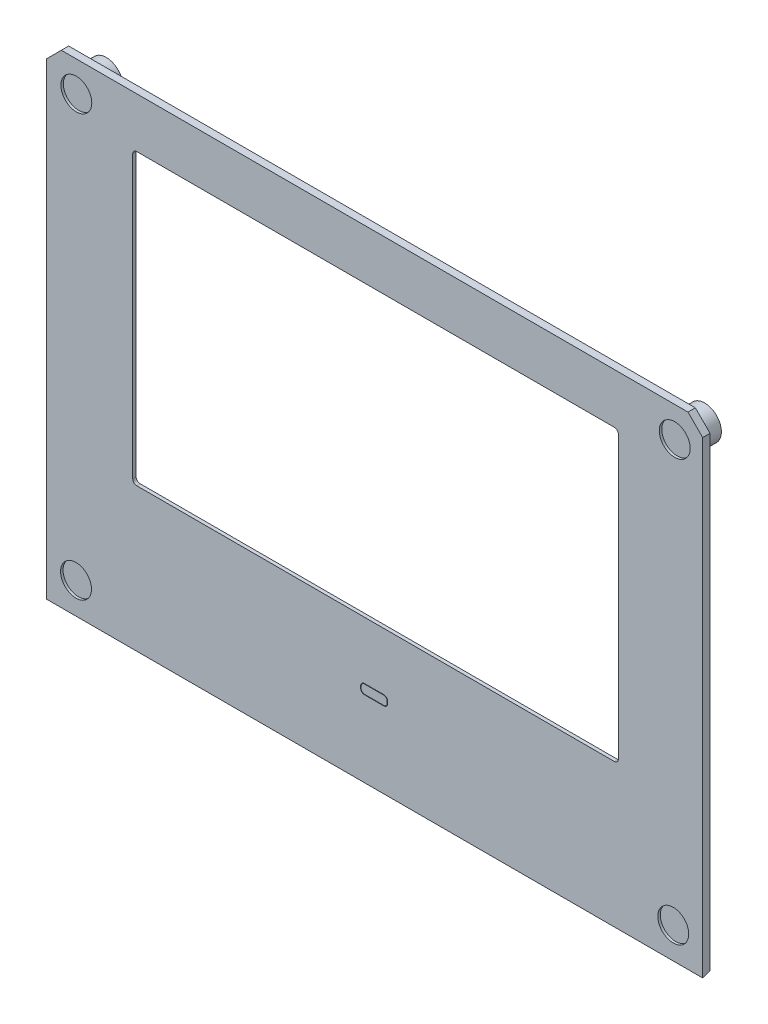
SolidWorks part; units mm, degrees
ref_plane "Front Plane" through (0, 0, 0) normal (0, 0, 1) x (1, 0, 0)
ref_plane "Top Plane" through (0, 0, 0) normal (0, 1, 0) x (1, 0, 0)
ref_plane "Right Plane" through (0, 0, 0) normal (1, 0, 0) x (0, 0, -1)
sketch "Sketch1" plane through (0, 0, 0) normal (0, 0, 1) x (1, 0, 0)
  line L0 (0, 0) -> (0, 2.5) construction
  line L2 (-49.5, -27) -> (49.5, -27)
  line L3 (-49.5, -27) -> (-49.5, 32)
  line L4 (-49.5, 32) -> (49.5, 32)
  line L5 (49.5, -27) -> (49.5, 32)
  line L6 (-49.5, -27) -> (49.5, 32) construction
  line L7 (-49.5, 32) -> (49.5, -27) construction
  line L16 (63.7, 42.2) -> (-64.0602, 42.2)
  line L17 (-64.0602, 42.2) -> (-67.0602, 39.2)
  line L18 (-67.0602, 39.2) -> (-67.0602, -42.1345)
  line L19 (-67.0602, -42.1345) -> (-67.0602, -55.3)
  line L20 (-67.0602, -55.3) -> (66.7, -55.3)
  line L21 (66.7, -55.3) -> (66.7, -42.1345)
  line L22 (66.7, -42.1345) -> (66.7, 39.2)
  line L23 (66.7, 39.2) -> (63.7, 42.2)
  dimension "D3" = 99
  dimension "D6" = 59
  dimension "D7" = 2.5
  dimension "D1" = 97.5
extrude "Boss-Extrude1" add sketch "Sketch1" along normal blind 1.5
sketch "Sketch2" plane through (-67.0602, 0, 0) normal (-1, 0, 0) x (0, 0, 1)
  line L1 (0, 39.2) -> (0, -55.3) construction
  line L2 (1.5684, -56.2492) -> (-60.7101, -33.5817)
  line L3 (1.5684, -56.2492) -> (-60.7101, -33.5817)
  line L4 (0, 39.2) -> (0, -55.3)
  line L5 (1.5, 39.2) -> (1.5, -55.3) construction
  line L6 (1.5, 39.2) -> (1.5, -55.3)
  line L7 (1.5, -55.3) -> (0, -55.3) construction
  line L8 (1.5, -55.3) -> (0, -55.3)
  line L9 (1.5, -55.3) -> (1.5, -56.4371)
  line L10 (0, -55.3) -> (0, -55.8912)
  line M3 (0, -55.3) -> (1.5, -55.3)
  dimension "D1" = 0.2
extrude "Boss-Extrude2" add sketch "Sketch2" against normal up to surface (133.7602 mm away) contours L10 L3 L9 M3 region at (-67.0602, -55.6447, 0.8548) up to face at (66.7, -8.05, 0.75)
sketch "Sketch3" plane through (0, 0, 0) normal (0, 0, -1) x (-1, 0, 0)
  line L0 (54.4999, -35.4999) -> (54.4999, 35.5001)
  line L1 (54.4999, 35.5001) -> (-54.5001, 35.5001)
  line L2 (-54.5001, 35.5001) -> (-54.5001, -35.4999)
  line L3 (-54.5001, -35.4999) -> (54.4999, -35.4999)
  line L4 (52.9999, -33.9999) -> (52.9999, 34.0001)
  line L5 (-53.0001, -33.9999) -> (52.9999, -33.9999)
  line L6 (-53.0001, 34.0001) -> (-53.0001, -33.9999)
  line L7 (52.9999, 34.0001) -> (-53.0001, 34.0001)
  line L8 (52.9999, -33.9999) -> (52.9999, 34.0001) construction
  line L9 (-53.0001, -33.9999) -> (52.9999, -33.9999) construction
  line L10 (-53.0001, 34.0001) -> (-53.0001, -33.9999) construction
  line L11 (52.9999, 34.0001) -> (-53.0001, 34.0001) construction
  dimension "D1" = 0
  dimension "D2" = 1.5
extrude "Cut-Extrude1" cut sketch "Sketch3" against normal blind 0.8
sketch "Sketch4" plane through (0, 0, 1.5) normal (0, 0, 1) x (1, 0, 0)
  circle A0 centre (60.7, -49.8912) radius 1.5 construction
  circle A1 centre (-61.0602, -49.8912) radius 1.5 construction
  circle A2 centre (60.7, -49.8912) radius 1.5
  circle A3 centre (-61.0602, -49.8912) radius 1.5
  spline S0 degree 3 poles (-62.625, 36) (-62.625, 32.75) (-59.375, 32.75) (-59.375, 36) (-59.375, 39.25) (-62.625, 39.25) (-62.625, 36) (-62.625, 32.75) (-59.375, 32.75) knots -0.5 0 0 0 0.5 0.5 0.5 1 1 1 1.5 1.5 1.5 weights 1 0.333333 0.333333 1 0.333333 0.333333 1 0.333333 0.333333 only from (-62.625, 36) to (-62.625, 36) construction
  spline S1 degree 3 poles (-62.625, 36) (-62.625, 32.75) (-59.375, 32.75) (-59.375, 36) (-59.375, 39.25) (-62.625, 39.25) (-62.625, 36) (-62.625, 32.75) (-59.375, 32.75) knots -0.5 0 0 0 0.5 0.5 0.5 1 1 1 1.5 1.5 1.5 weights 1 0.333333 0.333333 1 0.333333 0.333333 1 0.333333 0.333333 only from (-62.625, 36) to (-62.625, 36)
  spline S2 degree 3 poles (59.375, 36) (59.375, 32.75) (62.625, 32.75) (62.625, 36) (62.625, 39.25) (59.375, 39.25) (59.375, 36) (59.375, 32.75) (62.625, 32.75) knots -0.5 0 0 0 0.5 0.5 0.5 1 1 1 1.5 1.5 1.5 weights 1 0.333333 0.333333 1 0.333333 0.333333 1 0.333333 0.333333 only from (59.375, 36) to (59.375, 36) construction
  spline S3 degree 3 poles (59.375, 36) (59.375, 32.75) (62.625, 32.75) (62.625, 36) (62.625, 39.25) (59.375, 39.25) (59.375, 36) (59.375, 32.75) (62.625, 32.75) knots -0.5 0 0 0 0.5 0.5 0.5 1 1 1 1.5 1.5 1.5 weights 1 0.333333 0.333333 1 0.333333 0.333333 1 0.333333 0.333333 only from (59.375, 36) to (59.375, 36)
  spline S4 degree 3 poles (-62.625, -36) (-62.625, -39.25) (-59.375, -39.25) (-59.375, -36) (-59.375, -32.75) (-62.625, -32.75) (-62.625, -36) (-62.625, -39.25) (-59.375, -39.25) knots -0.5 0 0 0 0.5 0.5 0.5 1 1 1 1.5 1.5 1.5 weights 1 0.333333 0.333333 1 0.333333 0.333333 1 0.333333 0.333333 only from (-62.625, -36) to (-62.625, -36) construction
  spline S5 degree 3 poles (-62.625, -36) (-62.625, -39.25) (-59.375, -39.25) (-59.375, -36) (-59.375, -32.75) (-62.625, -32.75) (-62.625, -36) (-62.625, -39.25) (-59.375, -39.25) knots -0.5 0 0 0 0.5 0.5 0.5 1 1 1 1.5 1.5 1.5 weights 1 0.333333 0.333333 1 0.333333 0.333333 1 0.333333 0.333333 only from (-62.625, -36) to (-62.625, -36) construction
  spline S6 degree 3 poles (59.375, -36) (59.375, -39.25) (62.625, -39.25) (62.625, -36) (62.625, -32.75) (59.375, -32.75) (59.375, -36) (59.375, -39.25) (62.625, -39.25) knots -0.5 0 0 0 0.5 0.5 0.5 1 1 1 1.5 1.5 1.5 weights 1 0.333333 0.333333 1 0.333333 0.333333 1 0.333333 0.333333 only from (59.375, -36) to (59.375, -36) construction
  spline S7 degree 3 poles (59.375, -36) (59.375, -39.25) (62.625, -39.25) (62.625, -36) (62.625, -32.75) (59.375, -32.75) (59.375, -36) (59.375, -39.25) (62.625, -39.25) knots -0.5 0 0 0 0.5 0.5 0.5 1 1 1 1.5 1.5 1.5 weights 1 0.333333 0.333333 1 0.333333 0.333333 1 0.333333 0.333333 only from (59.375, -36) to (59.375, -36) construction
extrude "Cut-Extrude2" cut sketch "Sketch4" against normal blind 2
sketch "Sketch5" plane through (0, 0, 1.5) normal (0, 0, 1) x (1, 0, 0)
  line L4 (-57, 36) -> (-57, 40.2)
  line L5 (-57, 40.2) -> (-61, 40.2)
  line L6 (-65.2, 36) -> (-65.2, 32)
  line L7 (-65.2, 32) -> (-61, 32)
  line L8 (-57, 36) -> (-57, 40.2) construction
  line L9 (-57, 40.2) -> (-61, 40.2) construction
  line L10 (-65.2, 36) -> (-65.2, 32) construction
  line L11 (-65.2, 32) -> (-61, 32) construction
  line L12 (61, 40.2) -> (57, 40.2)
  line L13 (57, 40.2) -> (57, 36)
  line L14 (61, 32) -> (65.2, 32)
  line L15 (65.2, 32) -> (65.2, 36)
  line L16 (61, 40.2) -> (57, 40.2) construction
  line L17 (57, 40.2) -> (57, 36) construction
  line L18 (61, 32) -> (65.2, 32) construction
  line L19 (65.2, 32) -> (65.2, 36) construction
  circle A0 centre (-61, 36) radius 1.625 construction
  circle A1 centre (-61, 36) radius 1.625
  circle A2 centre (61, 36) radius 1.625 construction
  circle A3 centre (61, 36) radius 1.625
  arc A8 (-61, 40.2) -> (-65.2, 36) centre (-61.0002, 36.0002) ccw
  arc A9 (-61, 32) -> (-57, 36) centre (-61, 36) ccw
  arc A10 (-61, 40.2) -> (-65.2, 36) centre (-61.0002, 36.0002) ccw construction
  arc A11 (-61, 32) -> (-57, 36) centre (-61, 36) ccw construction
  arc A12 (65.2, 36) -> (61, 40.2) centre (61.0002, 36.0002) ccw
  arc A13 (57, 36) -> (61, 32) centre (61, 36) ccw
  arc A14 (65.2, 36) -> (61, 40.2) centre (61.0002, 36.0002) ccw construction
  arc A15 (57, 36) -> (61, 32) centre (61, 36) ccw construction
  circle A16 centre (-61, 36) radius 3.3998
  circle A17 centre (61.0002, 36.0002) radius 3.3998
  dimension "D3" = 0.8
  dimension "D1" = 0
  dimension "D2" = 0
extrude "Boss-Extrude3" add sketch "Sketch5" against normal offset from surface (6.1114 mm away) 1.7
sketch "Sketch6" plane through (0, 0, 1.5) normal (0, 0, 1) x (1, 0, 0)
  line L4 (3.5199, -36.2) -> (-11.8801, -36.2)
  line L5 (-11.8801, -36.2) -> (-11.8801, -48.2)
  line L6 (-11.8801, -48.2) -> (3.5199, -48.2)
  line L7 (3.5199, -48.2) -> (3.5199, -36.2)
  line L8 (3.5199, -36.2) -> (-11.8801, -36.2) construction
  line L9 (-11.8801, -36.2) -> (-11.8801, -48.2) construction
  line L10 (-11.8801, -48.2) -> (3.5199, -48.2) construction
  line L11 (3.5199, -48.2) -> (3.5199, -36.2) construction
  circle A0 centre (-0.2801, -39.7) radius 3.5
  circle A1 centre (-0.2801, -39.7) radius 2.5
  circle A2 centre (-0.2801, -39.7) radius 2.5 construction
  dimension "D3" = 7
  dimension "D1" = 0
  dimension "D2" = 0
extrude "Cut-Extrude5" cut sketch "Sketch6" against normal blind 10
sketch "Sketch7" plane through (0, 0, 1.5) normal (0, 0, 1) x (1, 0, 0)
  line L1 (-3.0301, -40.7) -> (2.4699, -40.7)
  line L2 (-3.0301, -40.7) -> (-3.0301, -38.7)
  line L3 (-3.0301, -38.7) -> (2.4699, -38.7)
  line L4 (2.4699, -40.7) -> (2.4699, -38.7)
  line L5 (-3.0301, -40.7) -> (2.4699, -38.7) construction
  line L6 (-3.0301, -38.7) -> (2.4699, -40.7) construction
  circle A0 centre (-0.2801, -39.7) radius 3.5 construction
  circle A1 centre (-0.2801, -39.7) radius 3.5
  dimension "D1" = 5.5
  dimension "D2" = 2
extrude "Boss-Extrude4" add sketch "Sketch7" against normal blind 0.8
fillet "Fillet1" radius 0.8 4 edges at (2.4699, -40.7, 1.1) (2.4699, -38.7, 1.1) (-3.0301, -40.7, 1.1) (-3.0301, -38.7, 1.1)
sketch "Sketch8" plane through (0, 0, 0.7) normal (0, 0, -1) x (-1, 0, 0)
  circle A0 centre (0.2801, -39.7) radius 3.25
  circle A1 centre (0.2801, -39.7) radius 3.5 construction
  dimension "D1" = 0.25
  dimension "D2" = 6.5
extrude "Boss-Extrude5" add sketch "Sketch8" along normal blind 1.5 separate body
sketch "Sketch9" plane through (0, 0, 0.7) normal (0, 0, 1) x (1, 0, 0)
  line L9 (2.3699, -39.9) -> (2.3699, -39.5)
  line L10 (-2.2301, -40.6) -> (1.6699, -40.6)
  line L11 (-2.9301, -39.5) -> (-2.9301, -39.9)
  line L12 (1.6699, -38.8) -> (-2.2301, -38.8)
  line L13 (2.3699, -39.9) -> (2.3699, -39.5)
  line L14 (-2.2301, -40.6) -> (1.6699, -40.6)
  line L15 (-2.9301, -39.5) -> (-2.9301, -39.9)
  line L16 (1.6699, -38.8) -> (-2.2301, -38.8)
  arc A8 (1.6699, -40.6) -> (2.3699, -39.9) centre (1.6699, -39.9) ccw
  arc A9 (-2.9301, -39.9) -> (-2.2301, -40.6) centre (-2.2301, -39.9) ccw
  arc A10 (-2.2301, -38.8) -> (-2.9301, -39.5) centre (-2.2301, -39.5) ccw
  arc A11 (2.3699, -39.5) -> (1.6699, -38.8) centre (1.6699, -39.5) ccw
  arc A12 (1.6699, -40.6) -> (2.3699, -39.9) centre (1.6699, -39.9) ccw
  arc A13 (-2.9301, -39.9) -> (-2.2301, -40.6) centre (-2.2301, -39.9) ccw
  arc A14 (-2.2301, -38.8) -> (-2.9301, -39.5) centre (-2.2301, -39.5) ccw
  arc A15 (2.3699, -39.5) -> (1.6699, -38.8) centre (1.6699, -39.5) ccw
  dimension "D1" = 0.1
extrude "Boss-Extrude6" add sketch "Sketch9" along normal up to surface (0.8 mm away) up to face at (-59.5602, -49.8912, 1.5)
fillet "Fillet2" radius 0.8 4 edges at (49.5, -27, 1.15) (-49.5, -27, 1.15) (-49.5, 32, 1.15) (49.5, 32, 1.15)
sketch "Sketch10" plane through (0, 0, 1.5) normal (0, 0, 1) x (1, 0, 0)
  circle A0 centre (-61, 36) radius 3.15
  circle A1 centre (-61.0602, -49.8912) radius 3.15
  circle A2 centre (60.7, -49.8912) radius 3.15
  circle A3 centre (61, 36) radius 3.15
  dimension "D1" = 6.3
extrude "Cut-Extrude6" cut sketch "Sketch10" against normal blind 0.5
sketch "Sketch11" plane through (0, 0, 0) normal (0, 0, -1) x (-1, 0, 0)
  line L0 (-63.7, 42.2) -> (64.0602, 42.2) construction
  line L1 (67.0602, 39.2) -> (67.0602, -55.6784) construction
  line L2 (64.3998, 36) -> (64.3998, -2.317) construction
  line L3 (54.4999, -35.4999) -> (54.4999, 35.5001) construction
  line L4 (59.5602, 22.2) -> (59.5602, 29) construction
  circle A0 centre (59.5602, 22.2) radius 5.05 construction
  circle A1 centre (61, 36) radius 3.3998 construction
  circle A2 centre (62.6498, 16.1424) radius 1.75
  circle A3 centre (56.2499, 16.2602) radius 1.75
  circle A4 centre (59.5602, 29) radius 1.75
  spline S0 degree 3 poles (61, 39.3998) (54.2004, 39.3998) (54.2004, 32.6002) (61, 32.6002) (67.7996, 32.6002) (67.7996, 39.3998) (61, 39.3998) (54.2004, 39.3998) (54.2004, 32.6002) knots -0.5 0 0 0 0.5 0.5 0.5 1 1 1 1.5 1.5 1.5 weights 1 0.333333 0.333333 1 0.333333 0.333333 1 0.333333 0.333333 only from (61, 39.3998) to (61, 39.3998) construction
  dimension "D1" = 10.1
  dimension "D4" = 3.5
  dimension "D2" = 20
  dimension "D3" = 7.5
extrude "Boss-Extrude7" add sketch "Sketch11" along normal offset from surface (4.2114 mm away) 0.4 up to face at (-61, 39.3998, -4.6114)
sketch "Sketch12" plane through (0, 0, 1) normal (0, 0, 1) x (1, 0, 0)
  circle A0 centre (-61, 36) radius 1.625 construction
  circle A1 centre (-61, 36) radius 1.625
  circle A2 centre (-61.0602, -49.8912) radius 1.5 construction
  circle A3 centre (-61.0602, -49.8912) radius 1.5
  circle A4 centre (61, 36) radius 1.625 construction
  circle A5 centre (61, 36) radius 1.625
  circle A6 centre (60.7, -49.8912) radius 1.5 construction
  circle A7 centre (60.7, -49.8912) radius 1.5
extrude "Boss-Extrude8" add sketch "Sketch12" against normal blind 0.3
